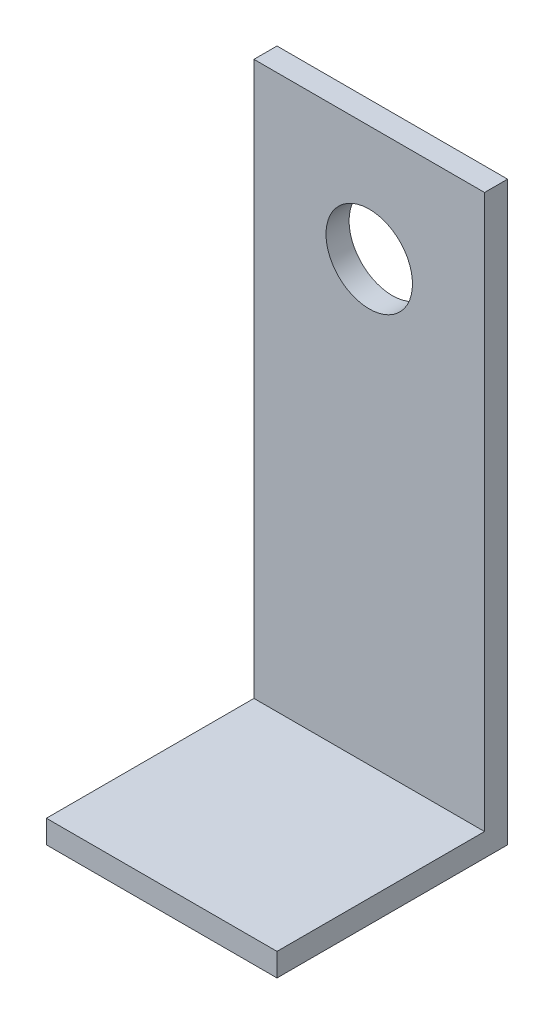
SolidWorks part; units mm, degrees
ref_plane "Front Plane" through (0, 0, 0) normal (0, 0, 1) x (1, 0, 0)
ref_plane "Top Plane" through (0, 0, 0) normal (0, 1, 0) x (1, 0, 0)
ref_plane "Right Plane" through (0, 0, 0) normal (1, 0, 0) x (0, 0, -1)
sketch "Sketch1" plane through (0, 0, 0) normal (1, 0, 0) x (0, 0, -1)
  line L0 (-25.4, 0) -> (0, 0)
  line L1 (0, 0) -> (0, 63.5)
  line L2 (-25.4, 0) -> (-25.4, 2.54)
  line L3 (-25.4, 2.54) -> (-2.54, 2.54)
  line L4 (-2.54, 2.54) -> (-2.54, 63.5)
  line L5 (-2.54, 63.5) -> (0, 63.5)
  dimension "D1" = 25.4
  dimension "D2" = 63.5
  dimension "D3" = 2.54
  dimension "D4" = 2.54
extrude "Boss-Extrude1" add sketch "Sketch1" along normal blind 12.7 and the other way blind 12.7
sketch "Sketch2" plane through (0, 0, 2.54) normal (0, 0, 1) x (1, 0, 0)
  line L0 (0, 63.5) -> (0, 0) construction
  line L1 (12.7, 63.5) -> (-12.7, 63.5) construction
  line L2 (-12.7, 0) -> (12.7, 0) construction
  circle A0 centre (0, 50.8) radius 4.7625
  dimension "D1" = 9.525
  dimension "D2" = 50.8
extrude "Cut-Extrude1" cut sketch "Sketch2" against normal blind 12.7
